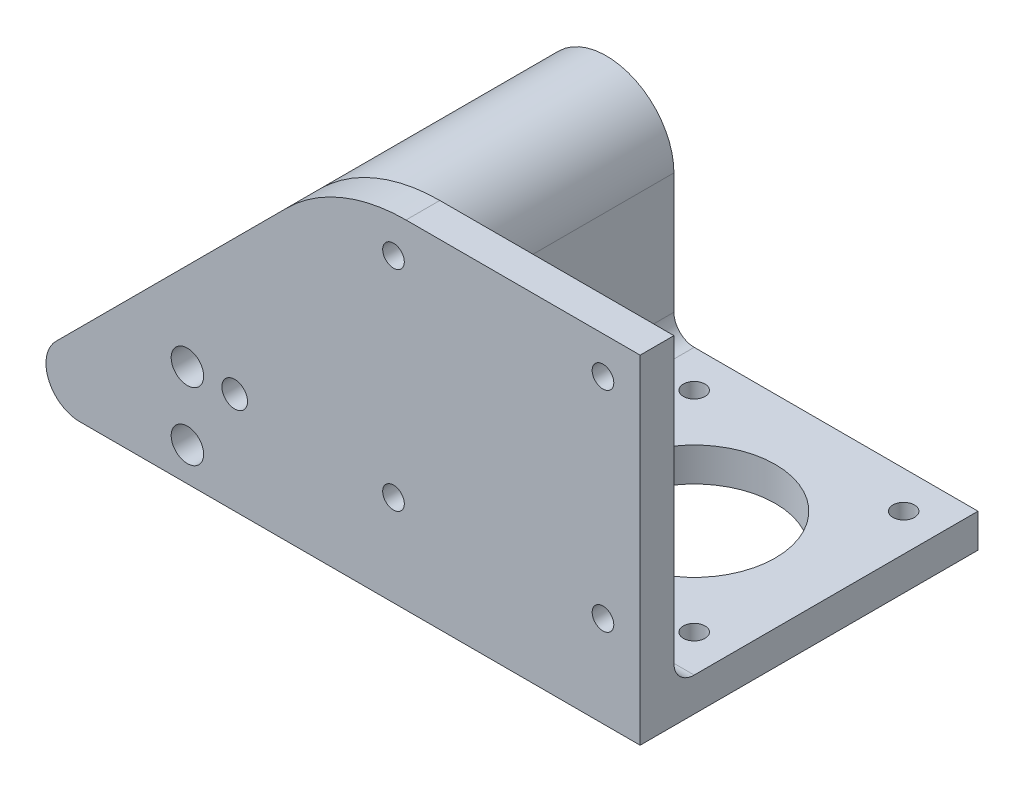
SolidWorks part; units mm, degrees
ref_plane "前视基准面" through (0, 0, 0) normal (0, 0, 1) x (1, 0, 0)
ref_plane "上视基准面" through (0, 0, 0) normal (0, 1, 0) x (1, 0, 0)
ref_plane "右视基准面" through (0, 0, 0) normal (1, 0, 0) x (0, 0, -1)
sketch "草图1" plane through (0, 0, 0) normal (0, 1, 0) x (1, 0, 0)
  line L0 (-24, -24) -> (-24, 21)
  line L1 (-21, -21) -> (21, -21) construction
  line L2 (-21, -21) -> (-21, 21) construction
  line L3 (-21, 21) -> (21, 21)
  line L4 (21, -21) -> (21, 21)
  line L5 (-21, -21) -> (21, 21) construction
  line L6 (-21, 21) -> (21, -21) construction
  line L7 (-15.5, -15.5) -> (15.5, -15.5) construction
  line L8 (-15.5, -15.5) -> (-15.5, 15.5) construction
  line L9 (-15.5, 15.5) -> (15.5, 15.5) construction
  line L10 (15.5, -15.5) -> (15.5, 15.5) construction
  line L11 (-15.5, -15.5) -> (15.5, 15.5) construction
  line L12 (-15.5, 15.5) -> (15.5, -15.5) construction
  line L13 (-21, -21) -> (21, -21) construction
  line L15 (-24, -24) -> (21, -24)
  line L16 (21, -21) -> (21, -24)
  line L17 (-24, 21) -> (-21, 21)
  circle A0 centre (-15.5, 15.5) radius 1.6
  circle A1 centre (15.5, 15.5) radius 1.6
  circle A2 centre (-15.5, -15.5) radius 1.6
  circle A3 centre (15.5, -15.5) radius 1.6
  circle A4 centre (0, 0) radius 12
  point P0 (0, 0)
  point P12 (0, 0)
  dimension "D3" = 3.2
  dimension "D4" = 3.2
  dimension "D5" = 3.2
  dimension "D6" = 3.2
  dimension "D9" = 24
  dimension "D1" = 42
  dimension "D2" = 42
  dimension "D7" = 31
  dimension "D8" = 3
  dimension "D10" = 3
extrude "凸台-拉伸1" add sketch "草图1" along normal blind 5
sketch "草图4" plane through (0, 0, 24) normal (0, 0, 1) x (1, 0, 0)
  line L0 (-21, 8) -> (21, 8) construction
  line L1 (-24, 0) -> (21, 0)
  line L2 (-24, 0) -> (-24, 50)
  line L3 (-24, 50) -> (21, 50)
  line L4 (21, 0) -> (21, 50)
  line L5 (21, 8) -> (-21, 50) construction
  line L6 (-21, 8) -> (21, 50) construction
  line L7 (21, 5) -> (21, 0) construction
  line L8 (-15.5, 13.5) -> (15.5, 13.5) construction
  line L9 (-15.5, 13.5) -> (-15.5, 44.5) construction
  line L10 (-15.5, 44.5) -> (15.5, 44.5) construction
  line L11 (15.5, 13.5) -> (15.5, 44.5) construction
  line L12 (-15.5, 13.5) -> (15.5, 44.5) construction
  line L13 (-15.5, 44.5) -> (15.5, 13.5) construction
  line L14 (-21, 50) -> (-21, 8) construction
  line L15 (-16, 29) -> (16, 29) construction
  circle A0 centre (-15.5, 44.5) radius 1.6
  circle A1 centre (15.5, 44.5) radius 1.6
  circle A2 centre (-15.5, 13.5) radius 1.6
  circle A3 centre (15.5, 13.5) radius 1.6
  point P7 (0, 29)
  dimension "D4" = 3.2
  dimension "D5" = 3.2
  dimension "D6" = 3.2
  dimension "D7" = 3.2
  dimension "D1" = 50
  dimension "D2" = 42
  dimension "D3" = 31
  dimension "D8" = 42
extrude "凸台-拉伸4" add sketch "草图4" along normal blind 5
sketch "草图5" plane through (-24, 0, 0) normal (-1, 0, 0) x (0, 0, 1)
  line L1 (29, 50) -> (-21, 50)
  line L2 (29, 50) -> (29, 0)
  line L3 (29, 0) -> (-21, 0)
  line L4 (-21, 50) -> (-21, 0)
extrude "凸台-拉伸5" add sketch "草图5" along normal blind 50
sketch "草图6" plane through (0, 0, -21) normal (0, 0, -1) x (-1, 0, 0)
  circle A0 centre (39, 15) radius 1.5 construction
  circle A1 centre (46, 5) radius 2 construction
  circle A2 centre (46, 15) radius 2 construction
  circle A3 centre (39, 15) radius 1.5 construction
  circle A4 centre (46, 5) radius 2 construction
  circle A5 centre (46, 15) radius 2 construction
  circle A6 centre (46, 15) radius 2.4
  circle A7 centre (39, 15) radius 1.9
  circle A8 centre (46, 5) radius 2.4
  dimension "D1" = 0.4
extrude "切除-拉伸1" cut sketch "草图6" against normal through all
sketch "草图7" plane through (0, 0, -21) normal (0, 0, -1) x (-1, 0, 0)
  line L0 (-21, 0) -> (74, 0) construction
  line L1 (51, 0) -> (34, 0)
  line L2 (51, 0) -> (51, 20)
  line L3 (51, 20) -> (34, 20)
  line L4 (34, 0) -> (34, 20)
  line L5 (24, 50) -> (24, 5) construction
  circle A1 centre (46, 15) radius 2.4 construction
  dimension "D1" = 20
  dimension "D2" = 10
  dimension "D3" = 17
extrude "切除-拉伸2" cut sketch "草图7" against normal offset from surface (45 mm away) 5 up to face at (-48.4, 5, 29)
sketch "草图8" plane through (0, 0, 0) normal (0, -1, 0) x (1, 0, 0)
  circle A0 centre (-60.5, 19) radius 1.8 construction
  circle A1 centre (-60.5, 19) radius 1.8
extrude "切除-拉伸3" cut sketch "草图8" against normal through all
sketch "草图9" plane through (0, 50, 0) normal (0, 1, 0) x (1, 0, 0)
  circle A0 centre (-60.5, -19) radius 1.8 construction
  circle A1 centre (-60.5, -19) radius 1.8 construction
  circle A2 centre (-60.5, -19) radius 2.8
  dimension "D1" = 1
extrude "切除-拉伸4" cut sketch "草图9" against normal offset from surface (45 mm away) 5 up to face at (-60.5, 0, 17.2)
chamfer "倒角1" distance 50 angle 45 1 edges at (-74, 50, 4)
fillet "圆角1" radius 5 1 edges at (-74, 0, 4)
fillet "圆角2" radius 10 1 edges at (-24, 50, 1.5) type face fillet first side face at (-40.5858, 33.4142, 8) second side face at (-24, 27.5, 1.5)
fillet "圆角4" radius 25 1 edges at (-24, 50, 26.5)
fillet "圆角5" radius 3 6 edges at (-1.5, 5, 24) (-24, 5, 1.5) (-30.1732, 35.0967, 24) (-24, 15.4289, 24) (-34, 20, 1.5) (-51, 20, 1.5)
fillet "圆角6" radius 1.5 5 edges at (-34, 8.5, 24) (-34.8787, 19.1213, 24) (-42.5, 20, 24) (-50.1213, 19.1213, 24) (-51, 8.5, 24)
